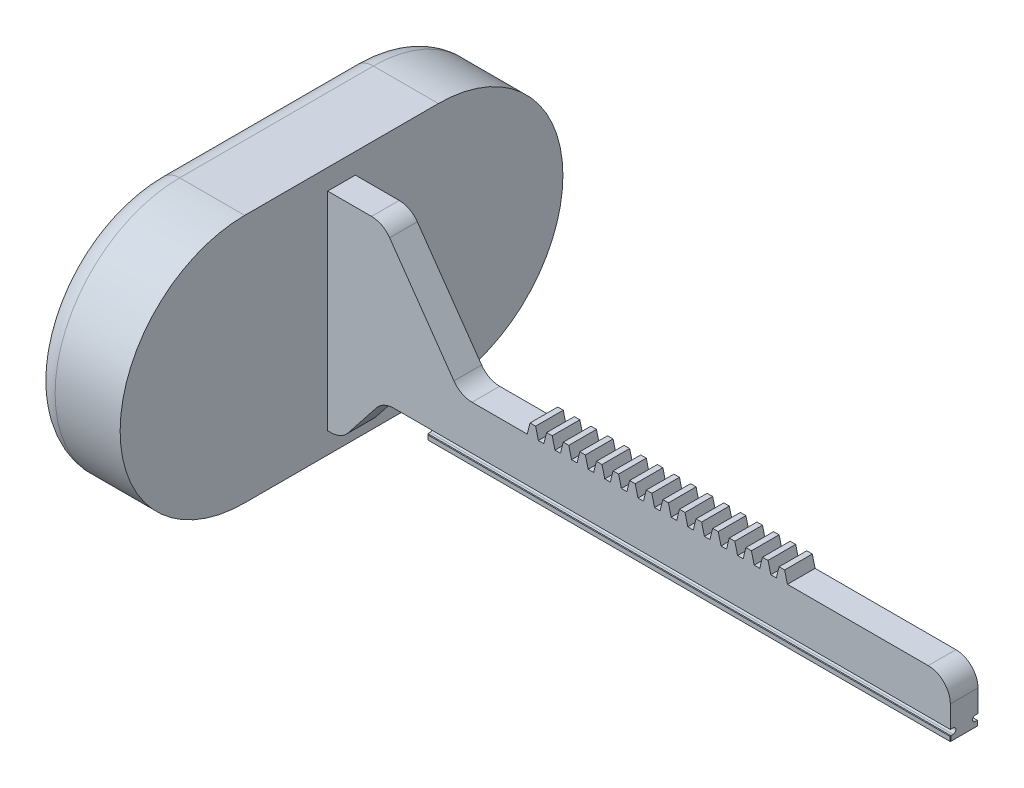
SolidWorks part; units mm, degrees
ref_plane "Front Plane" through (0, 0, 0) normal (0, 0, 1) x (1, 0, 0)
ref_plane "Top Plane" through (0, 0, 0) normal (0, 1, 0) x (1, 0, 0)
ref_plane "Right Plane" through (0, 0, 0) normal (1, 0, 0) x (0, 0, -1)
sketch "Sketch1" plane through (0, 0, 0) normal (0, 0, 1) x (1, 0, 0)
  line L0 (-71.4375, 23.8125) -> (-58.7375, 23.8125)
  line L1 (-71.4375, -23.8125) -> (71.4375, -23.8125) construction
  line L2 (-71.4375, -23.8125) -> (-71.4375, 23.8125) construction
  line L3 (-71.4375, 23.8125) -> (71.4375, 23.8125) construction
  line L4 (71.4375, -23.8125) -> (71.4375, 23.8125) construction
  line L5 (-71.4375, -23.8125) -> (71.4375, 23.8125) construction
  line L6 (-71.4375, 23.8125) -> (71.4375, -23.8125) construction
  line L7 (-58.7375, 23.8125) -> (-40.9575, -1.5875)
  line L8 (-40.9575, -1.5875) -> (71.4375, -1.5875)
  line L9 (71.4375, -1.5875) -> (71.4375, -14.2875)
  line L10 (71.4375, -14.2875) -> (-48.5775, -14.2875)
  line L12 (-68.2625, -23.8125) -> (-71.4375, -23.8125)
  line L13 (-71.4375, 23.8125) -> (-71.4375, -23.8125)
  line L14 (-48.5775, -14.2875) -> (-48.5775, -11.7475)
  line L15 (-48.5775, -11.7475) -> (-58.7375, -11.7475)
  line L16 (-58.7375, -11.7475) -> (-68.2625, -23.8125)
  point P0 (0, 0)
  dimension "D1" = 142.875
  dimension "D2" = 47.625
  dimension "D3" = 25.4
  dimension "D4" = 12.7
  dimension "D5" = 2.54
  dimension "D6" = 12.7
  dimension "D7" = 3.175
  dimension "D8" = 17.78
  dimension "D9" = 10.16
extrude "Boss-Extrude1" add sketch "Sketch1" along normal blind 6.35
fillet "Fillet1" radius 5.08 1 edges at (-58.7375, 23.8125, 3.175)
fillet "Fillet2" radius 5.08 3 edges at (-68.2625, -23.8125, 3.175) (-58.7375, -11.7475, 3.175) (-40.9575, -1.5875, 3.175)
fillet "Fillet3" radius 5.08 1 edges at (71.4375, -1.5875, 3.175)
sketch "Sketch2" plane through (71.4375, 0, 0) normal (1, 0, 0) x (0, 0, -1)
  line L0 (-6.35, -11.7475) -> (-5.08, -11.7475)
  line L1 (-6.35, -14.2875) -> (-6.35, -6.6675) construction
  line L2 (-5.08, -11.7475) -> (-5.08, -13.0175)
  line L3 (-5.08, -13.0175) -> (-6.35, -13.0175)
  line L4 (-6.35, -13.0175) -> (-6.35, -11.7475)
  line L5 (-6.35, -14.2875) -> (0, -14.2875) construction
  line L6 (-1.27, -11.7475) -> (-1.27, -13.0175)
  line L7 (-1.27, -13.0175) -> (0, -13.0175)
  line L12 (0, -14.2875) -> (0, -6.6675) construction
  line L13 (0, -13.0175) -> (0, -11.7475)
  line L14 (0, -11.7475) -> (-1.27, -11.7475)
  point P10 (-0.635, -13.0175)
  dimension "D1" = 1.27
  dimension "D2" = 1.27
  dimension "D3" = 1.27
  dimension "D4" = 1.27
  dimension "D5" = 1.27
  dimension "D6" = 1.27
extrude "Cut-Extrude1" cut sketch "Sketch2" against normal up to surface (120.015 mm away) up to face at (-48.5775, -13.0175, 3.175)
fillet "Fillet5" 2 edges at (11.43, -13.0175, 1.27) (11.43, -11.7475, 1.27) type full round first side face at (11.43, -13.0175, 0.635) second side face at (9.5054, -11.7475, 3.175) middle face at (11.43, -12.3825, 1.27)
fillet "Fillet6" 2 edges at (11.43, -11.7475, 5.08) (11.43, -13.0175, 5.08) type full round first side face at (9.5054, -11.7475, 3.0163) second side face at (11.43, -13.0175, 5.715) middle face at (11.43, -12.3825, 5.08)
chamfer "Chamfer1" distance 0.127 angle 45 9 edges at (-48.5775, -13.6525, 0) (11.43, -14.2875, 0) (11.43, -13.0175, 0) (71.4375, -13.6525, 0) (11.43, -14.2875, 6.35) (-48.5775, -13.6525, 6.35) (11.43, -13.0175, 6.35) (71.4375, -13.6525, 6.35) (71.4375, -14.2875, 3.175)
sketch "Sketch3" plane through (0, 0, 6.35) normal (0, 0, 1) x (1, 0, 0)
  line L0 (-10.3968, -1.5875) -> (-9.7618, 0.9525)
  line L1 (66.3575, -1.5875) -> (-38.3126, -1.5875) construction
  line L2 (-9.7618, 0.9525) -> (-8.4918, 0.9525)
  line L3 (-8.4918, 0.9525) -> (-7.8568, -1.5875)
  line L4 (-10.3968, -1.5875) -> (-7.8568, -1.5875)
  line L5 (-14.2068, -1.5875) -> (-13.5718, 0.9525)
  line L6 (-13.5718, 0.9525) -> (-12.3018, 0.9525)
  line L7 (-12.3018, 0.9525) -> (-11.6668, -1.5875)
  line L8 (-14.2068, -1.5875) -> (-11.6668, -1.5875)
  line L9 (-18.0168, -1.5875) -> (-17.3818, 0.9525)
  line L10 (-17.3818, 0.9525) -> (-16.1118, 0.9525)
  line L11 (-16.1118, 0.9525) -> (-15.4768, -1.5875)
  line L12 (-18.0168, -1.5875) -> (-15.4768, -1.5875)
  line L13 (-21.8268, -1.5875) -> (-21.1918, 0.9525)
  line L14 (-21.1918, 0.9525) -> (-19.9218, 0.9525)
  line L15 (-19.9218, 0.9525) -> (-19.2868, -1.5875)
  line L16 (-21.8268, -1.5875) -> (-19.2868, -1.5875)
  line L17 (-25.6368, -1.5875) -> (-25.0018, 0.9525)
  line L18 (-25.0018, 0.9525) -> (-23.7318, 0.9525)
  line L19 (-23.7318, 0.9525) -> (-23.0968, -1.5875)
  line L20 (-25.6368, -1.5875) -> (-23.0968, -1.5875)
  line L21 (-10.3968, -1.5875) -> (-9.7618, 0.9525)
  line L22 (-9.7618, 0.9525) -> (-8.4918, 0.9525)
  line L23 (-8.4918, 0.9525) -> (-7.8568, -1.5875)
  line L24 (-10.3968, -1.5875) -> (-7.8568, -1.5875)
  line L25 (-14.2068, -1.5875) -> (-13.5718, 0.9525)
  line L26 (-13.5718, 0.9525) -> (-12.3018, 0.9525)
  line L27 (-12.3018, 0.9525) -> (-11.6668, -1.5875)
  line L28 (-14.2068, -1.5875) -> (-11.6668, -1.5875)
  line L29 (-18.0168, -1.5875) -> (-17.3818, 0.9525)
  line L30 (-17.3818, 0.9525) -> (-16.1118, 0.9525)
  line L31 (-16.1118, 0.9525) -> (-15.4768, -1.5875)
  line L32 (-18.0168, -1.5875) -> (-15.4768, -1.5875)
  line L33 (-21.8268, -1.5875) -> (-21.1918, 0.9525)
  line L34 (-21.1918, 0.9525) -> (-19.9218, 0.9525)
  line L35 (-19.9218, 0.9525) -> (-19.2868, -1.5875)
  line L36 (-21.8268, -1.5875) -> (-19.2868, -1.5875)
  line L37 (-6.5868, -1.5875) -> (-5.9518, 0.9525)
  line L38 (-5.9518, 0.9525) -> (-4.6818, 0.9525)
  line L39 (-4.6818, 0.9525) -> (-4.0468, -1.5875)
  line L40 (-6.5868, -1.5875) -> (-4.0468, -1.5875)
  line L41 (-10.3968, -1.5875) -> (-9.7618, 0.9525)
  line L42 (-9.7618, 0.9525) -> (-8.4918, 0.9525)
  line L43 (-8.4918, 0.9525) -> (-7.8568, -1.5875)
  line L44 (-10.3968, -1.5875) -> (-7.8568, -1.5875)
  line L45 (-14.2068, -1.5875) -> (-13.5718, 0.9525)
  line L46 (-13.5718, 0.9525) -> (-12.3018, 0.9525)
  line L47 (-12.3018, 0.9525) -> (-11.6668, -1.5875)
  line L48 (-14.2068, -1.5875) -> (-11.6668, -1.5875)
  line L49 (-18.0168, -1.5875) -> (-17.3818, 0.9525)
  line L50 (-17.3818, 0.9525) -> (-16.1118, 0.9525)
  line L51 (-16.1118, 0.9525) -> (-15.4768, -1.5875)
  line L52 (-18.0168, -1.5875) -> (-15.4768, -1.5875)
  line L53 (-2.7768, -1.5875) -> (-2.1418, 0.9525)
  line L54 (-2.1418, 0.9525) -> (-0.8718, 0.9525)
  line L55 (-0.8718, 0.9525) -> (-0.2368, -1.5875)
  line L56 (-2.7768, -1.5875) -> (-0.2368, -1.5875)
  line L57 (-6.5868, -1.5875) -> (-5.9518, 0.9525)
  line L58 (-5.9518, 0.9525) -> (-4.6818, 0.9525)
  line L59 (-4.6818, 0.9525) -> (-4.0468, -1.5875)
  line L60 (-6.5868, -1.5875) -> (-4.0468, -1.5875)
  line L61 (-10.3968, -1.5875) -> (-9.7618, 0.9525)
  line L62 (-9.7618, 0.9525) -> (-8.4918, 0.9525)
  line L63 (-8.4918, 0.9525) -> (-7.8568, -1.5875)
  line L64 (-10.3968, -1.5875) -> (-7.8568, -1.5875)
  line L65 (-14.2068, -1.5875) -> (-13.5718, 0.9525)
  line L66 (-13.5718, 0.9525) -> (-12.3018, 0.9525)
  line L67 (-12.3018, 0.9525) -> (-11.6668, -1.5875)
  line L68 (-14.2068, -1.5875) -> (-11.6668, -1.5875)
  line L69 (1.0332, -1.5875) -> (1.6682, 0.9525)
  line L70 (1.6682, 0.9525) -> (2.9382, 0.9525)
  line L71 (2.9382, 0.9525) -> (3.5732, -1.5875)
  line L72 (1.0332, -1.5875) -> (3.5732, -1.5875)
  line L73 (-2.7768, -1.5875) -> (-2.1418, 0.9525)
  line L74 (-2.1418, 0.9525) -> (-0.8718, 0.9525)
  line L75 (-0.8718, 0.9525) -> (-0.2368, -1.5875)
  line L76 (-2.7768, -1.5875) -> (-0.2368, -1.5875)
  line L77 (-6.5868, -1.5875) -> (-5.9518, 0.9525)
  line L78 (-5.9518, 0.9525) -> (-4.6818, 0.9525)
  line L79 (-4.6818, 0.9525) -> (-4.0468, -1.5875)
  line L80 (-6.5868, -1.5875) -> (-4.0468, -1.5875)
  line L81 (-10.3968, -1.5875) -> (-9.7618, 0.9525)
  line L82 (-9.7618, 0.9525) -> (-8.4918, 0.9525)
  line L83 (-8.4918, 0.9525) -> (-7.8568, -1.5875)
  line L84 (-10.3968, -1.5875) -> (-7.8568, -1.5875)
  line L85 (4.8432, -1.5875) -> (5.4782, 0.9525)
  line L86 (5.4782, 0.9525) -> (6.7482, 0.9525)
  line L87 (6.7482, 0.9525) -> (7.3832, -1.5875)
  line L88 (4.8432, -1.5875) -> (7.3832, -1.5875)
  line L89 (1.0332, -1.5875) -> (1.6682, 0.9525)
  line L90 (1.6682, 0.9525) -> (2.9382, 0.9525)
  line L91 (2.9382, 0.9525) -> (3.5732, -1.5875)
  line L92 (1.0332, -1.5875) -> (3.5732, -1.5875)
  line L93 (-2.7768, -1.5875) -> (-2.1418, 0.9525)
  line L94 (-2.1418, 0.9525) -> (-0.8718, 0.9525)
  line L95 (-0.8718, 0.9525) -> (-0.2368, -1.5875)
  line L96 (-2.7768, -1.5875) -> (-0.2368, -1.5875)
  line L97 (-6.5868, -1.5875) -> (-5.9518, 0.9525)
  line L98 (-5.9518, 0.9525) -> (-4.6818, 0.9525)
  line L99 (-4.6818, 0.9525) -> (-4.0468, -1.5875)
  line L100 (-6.5868, -1.5875) -> (-4.0468, -1.5875)
  line L101 (8.6532, -1.5875) -> (9.2882, 0.9525)
  line L102 (9.2882, 0.9525) -> (10.5582, 0.9525)
  line L103 (10.5582, 0.9525) -> (11.1932, -1.5875)
  line L104 (8.6532, -1.5875) -> (11.1932, -1.5875)
  line L105 (4.8432, -1.5875) -> (5.4782, 0.9525)
  line L106 (5.4782, 0.9525) -> (6.7482, 0.9525)
  line L107 (6.7482, 0.9525) -> (7.3832, -1.5875)
  line L108 (4.8432, -1.5875) -> (7.3832, -1.5875)
  line L109 (1.0332, -1.5875) -> (1.6682, 0.9525)
  line L110 (1.6682, 0.9525) -> (2.9382, 0.9525)
  line L111 (2.9382, 0.9525) -> (3.5732, -1.5875)
  line L112 (1.0332, -1.5875) -> (3.5732, -1.5875)
  line L113 (-2.7768, -1.5875) -> (-2.1418, 0.9525)
  line L114 (-2.1418, 0.9525) -> (-0.8718, 0.9525)
  line L115 (-0.8718, 0.9525) -> (-0.2368, -1.5875)
  line L116 (-2.7768, -1.5875) -> (-0.2368, -1.5875)
  line L117 (12.4632, -1.5875) -> (13.0982, 0.9525)
  line L118 (13.0982, 0.9525) -> (14.3682, 0.9525)
  line L119 (14.3682, 0.9525) -> (15.0032, -1.5875)
  line L120 (12.4632, -1.5875) -> (15.0032, -1.5875)
  line L121 (8.6532, -1.5875) -> (9.2882, 0.9525)
  line L122 (9.2882, 0.9525) -> (10.5582, 0.9525)
  line L123 (10.5582, 0.9525) -> (11.1932, -1.5875)
  line L124 (8.6532, -1.5875) -> (11.1932, -1.5875)
  line L125 (4.8432, -1.5875) -> (5.4782, 0.9525)
  line L126 (5.4782, 0.9525) -> (6.7482, 0.9525)
  line L127 (6.7482, 0.9525) -> (7.3832, -1.5875)
  line L128 (4.8432, -1.5875) -> (7.3832, -1.5875)
  line L129 (1.0332, -1.5875) -> (1.6682, 0.9525)
  line L130 (1.6682, 0.9525) -> (2.9382, 0.9525)
  line L131 (2.9382, 0.9525) -> (3.5732, -1.5875)
  line L132 (1.0332, -1.5875) -> (3.5732, -1.5875)
  line L133 (16.2732, -1.5875) -> (16.9082, 0.9525)
  line L134 (16.9082, 0.9525) -> (18.1782, 0.9525)
  line L135 (18.1782, 0.9525) -> (18.8132, -1.5875)
  line L136 (16.2732, -1.5875) -> (18.8132, -1.5875)
  line L137 (12.4632, -1.5875) -> (13.0982, 0.9525)
  line L138 (13.0982, 0.9525) -> (14.3682, 0.9525)
  line L139 (14.3682, 0.9525) -> (15.0032, -1.5875)
  line L140 (12.4632, -1.5875) -> (15.0032, -1.5875)
  line L141 (8.6532, -1.5875) -> (9.2882, 0.9525)
  line L142 (9.2882, 0.9525) -> (10.5582, 0.9525)
  line L143 (10.5582, 0.9525) -> (11.1932, -1.5875)
  line L144 (8.6532, -1.5875) -> (11.1932, -1.5875)
  line L145 (4.8432, -1.5875) -> (5.4782, 0.9525)
  line L146 (5.4782, 0.9525) -> (6.7482, 0.9525)
  line L147 (6.7482, 0.9525) -> (7.3832, -1.5875)
  line L148 (4.8432, -1.5875) -> (7.3832, -1.5875)
  line L149 (20.0832, -1.5875) -> (20.7182, 0.9525)
  line L150 (20.7182, 0.9525) -> (21.9882, 0.9525)
  line L151 (21.9882, 0.9525) -> (22.6232, -1.5875)
  line L152 (20.0832, -1.5875) -> (22.6232, -1.5875)
  line L153 (16.2732, -1.5875) -> (16.9082, 0.9525)
  line L154 (16.9082, 0.9525) -> (18.1782, 0.9525)
  line L155 (18.1782, 0.9525) -> (18.8132, -1.5875)
  line L156 (16.2732, -1.5875) -> (18.8132, -1.5875)
  line L157 (12.4632, -1.5875) -> (13.0982, 0.9525)
  line L158 (13.0982, 0.9525) -> (14.3682, 0.9525)
  line L159 (14.3682, 0.9525) -> (15.0032, -1.5875)
  line L160 (12.4632, -1.5875) -> (15.0032, -1.5875)
  line L161 (8.6532, -1.5875) -> (9.2882, 0.9525)
  line L162 (9.2882, 0.9525) -> (10.5582, 0.9525)
  line L163 (10.5582, 0.9525) -> (11.1932, -1.5875)
  line L164 (8.6532, -1.5875) -> (11.1932, -1.5875)
  line L165 (23.8932, -1.5875) -> (24.5282, 0.9525)
  line L166 (24.5282, 0.9525) -> (25.7982, 0.9525)
  line L167 (25.7982, 0.9525) -> (26.4332, -1.5875)
  line L168 (23.8932, -1.5875) -> (26.4332, -1.5875)
  line L169 (20.0832, -1.5875) -> (20.7182, 0.9525)
  line L170 (20.7182, 0.9525) -> (21.9882, 0.9525)
  line L171 (21.9882, 0.9525) -> (22.6232, -1.5875)
  line L172 (20.0832, -1.5875) -> (22.6232, -1.5875)
  line L173 (16.2732, -1.5875) -> (16.9082, 0.9525)
  line L174 (16.9082, 0.9525) -> (18.1782, 0.9525)
  line L175 (18.1782, 0.9525) -> (18.8132, -1.5875)
  line L176 (16.2732, -1.5875) -> (18.8132, -1.5875)
  line L177 (12.4632, -1.5875) -> (13.0982, 0.9525)
  line L178 (13.0982, 0.9525) -> (14.3682, 0.9525)
  line L179 (14.3682, 0.9525) -> (15.0032, -1.5875)
  line L180 (12.4632, -1.5875) -> (15.0032, -1.5875)
  line L181 (27.7032, -1.5875) -> (28.3382, 0.9525)
  line L182 (28.3382, 0.9525) -> (29.6082, 0.9525)
  line L183 (29.6082, 0.9525) -> (30.2432, -1.5875)
  line L184 (27.7032, -1.5875) -> (30.2432, -1.5875)
  line L185 (23.8932, -1.5875) -> (24.5282, 0.9525)
  line L186 (24.5282, 0.9525) -> (25.7982, 0.9525)
  line L187 (25.7982, 0.9525) -> (26.4332, -1.5875)
  line L188 (23.8932, -1.5875) -> (26.4332, -1.5875)
  line L189 (20.0832, -1.5875) -> (20.7182, 0.9525)
  line L190 (20.7182, 0.9525) -> (21.9882, 0.9525)
  line L191 (21.9882, 0.9525) -> (22.6232, -1.5875)
  line L192 (20.0832, -1.5875) -> (22.6232, -1.5875)
  line L193 (16.2732, -1.5875) -> (16.9082, 0.9525)
  line L194 (16.9082, 0.9525) -> (18.1782, 0.9525)
  line L195 (18.1782, 0.9525) -> (18.8132, -1.5875)
  line L196 (16.2732, -1.5875) -> (18.8132, -1.5875)
  line L197 (-6.5868, -1.5875) -> (-5.9518, 0.9525)
  line L198 (-5.9518, 0.9525) -> (-4.6818, 0.9525)
  line L199 (-4.6818, 0.9525) -> (-4.0468, -1.5875)
  line L200 (-6.5868, -1.5875) -> (-4.0468, -1.5875)
  line L201 (-2.7768, -1.5875) -> (-2.1418, 0.9525)
  line L202 (-2.1418, 0.9525) -> (-0.8718, 0.9525)
  line L203 (-0.8718, 0.9525) -> (-0.2368, -1.5875)
  line L204 (-2.7768, -1.5875) -> (-0.2368, -1.5875)
  line L205 (1.0332, -1.5875) -> (1.6682, 0.9525)
  line L206 (1.6682, 0.9525) -> (2.9382, 0.9525)
  line L207 (2.9382, 0.9525) -> (3.5732, -1.5875)
  line L208 (1.0332, -1.5875) -> (3.5732, -1.5875)
  line L209 (4.8432, -1.5875) -> (5.4782, 0.9525)
  line L210 (5.4782, 0.9525) -> (6.7482, 0.9525)
  line L211 (6.7482, 0.9525) -> (7.3832, -1.5875)
  line L212 (4.8432, -1.5875) -> (7.3832, -1.5875)
  line L213 (8.6532, -1.5875) -> (9.2882, 0.9525)
  line L214 (9.2882, 0.9525) -> (10.5582, 0.9525)
  line L215 (10.5582, 0.9525) -> (11.1932, -1.5875)
  line L216 (8.6532, -1.5875) -> (11.1932, -1.5875)
  line L217 (12.4632, -1.5875) -> (13.0982, 0.9525)
  line L218 (13.0982, 0.9525) -> (14.3682, 0.9525)
  line L219 (14.3682, 0.9525) -> (15.0032, -1.5875)
  line L220 (12.4632, -1.5875) -> (15.0032, -1.5875)
  line L221 (16.2732, -1.5875) -> (16.9082, 0.9525)
  line L222 (16.9082, 0.9525) -> (18.1782, 0.9525)
  line L223 (18.1782, 0.9525) -> (18.8132, -1.5875)
  line L224 (16.2732, -1.5875) -> (18.8132, -1.5875)
  line L225 (20.0832, -1.5875) -> (20.7182, 0.9525)
  line L226 (20.7182, 0.9525) -> (21.9882, 0.9525)
  line L227 (21.9882, 0.9525) -> (22.6232, -1.5875)
  line L228 (20.0832, -1.5875) -> (22.6232, -1.5875)
  line L229 (23.8932, -1.5875) -> (24.5282, 0.9525)
  line L230 (24.5282, 0.9525) -> (25.7982, 0.9525)
  line L231 (25.7982, 0.9525) -> (26.4332, -1.5875)
  line L232 (23.8932, -1.5875) -> (26.4332, -1.5875)
  line L233 (27.7032, -1.5875) -> (28.3382, 0.9525)
  line L234 (28.3382, 0.9525) -> (29.6082, 0.9525)
  line L235 (29.6082, 0.9525) -> (30.2432, -1.5875)
  line L236 (27.7032, -1.5875) -> (30.2432, -1.5875)
  line L237 (31.5132, -1.5875) -> (32.1482, 0.9525)
  line L238 (32.1482, 0.9525) -> (33.4182, 0.9525)
  line L239 (33.4182, 0.9525) -> (34.0532, -1.5875)
  line L240 (31.5132, -1.5875) -> (34.0532, -1.5875)
  point P4 (-9.1268, -1.5875)
  point P7 (-9.1268, 0.9525)
  line M244 (66.3575, -1.5875) -> (-38.3126, -1.5875)
  dimension "D1" = 2.54
  dimension "D2" = 2.54
  dimension "D3" = 1.27
  dimension "D4" = 5
  dimension "D5" = 12
extrude "Boss-Extrude2" add sketch "Sketch3" against normal up to surface (6.35 mm away) contours L11 L10 L9 M244 | L87 L86 L85 M244 | L17 L18 L19 L20 | L13 L14 L15 L16 | L7 L8 L5 L6 | L3 L4 L0 L2 | L39 L40 L37 L38 | L53 L54 L55 L56 | L71 L72 L69 L70 | L103 L104 L101 L102 | L119 L120 L117 L118 | L135 L136 L133 L134 | L151 L152 L149 L150 | L167 L168 L165 L166 | L181 L182 L183 L184 | L239 L240 L237 L238 region at (6.1132, -0.4586, 6.35) region at (-16.7468, -0.4586, 6.35) up to face at (-29.6908, -3.5093, 0)
sketch "Sketch4" plane through (-71.4375, 0, 0) normal (-1, 0, 0) x (0, 0, 1)
  line L0 (6.35, 23.8125) -> (0, 23.8125) construction
  line L1 (-47.625, -28.6385) -> (53.975, -28.6385)
  line L2 (-47.625, -28.6385) -> (-47.625, 28.5115)
  line L3 (-47.625, 28.5115) -> (53.975, 28.5115)
  line L4 (53.975, -28.6385) -> (53.975, 28.5115)
  line L5 (-47.625, -28.6385) -> (53.975, 28.5115) construction
  line L6 (-47.625, 28.5115) -> (53.975, -28.6385) construction
  point P0 (3.175, -0.0635)
  point P7 (3.175, 23.8125)
  dimension "D1" = 101.6
  dimension "D2" = 57.15
  dimension "D3" = 23.876
extrude "Boss-Extrude3" add sketch "Sketch4" along normal blind 20 separate body
fillet "Fillet7" 2 edges at (-81.4375, 28.5115, -47.625) (-81.4375, -28.6385, -47.625) type full round first side face at (-81.4375, 28.5115, 3.175) second side face at (-81.4375, -28.6385, 3.175) middle face at (-81.4375, -0.0635, -47.625)
fillet "Fillet8" 2 edges at (-81.4375, 28.5115, 53.975) (-81.4375, -28.6385, 53.975) type full round first side face at (-81.4375, 28.5115, 17.4625) second side face at (-81.4375, -28.6385, 17.4625) middle face at (-81.4375, -0.0635, 53.975)
fillet "Fillet9" radius 5.08 4 edges at (-91.4375, -0.0635, -47.625) (-91.4375, 28.5115, 3.175) (-91.4375, -0.0635, 53.975) (-91.4375, -28.6385, 3.175)
